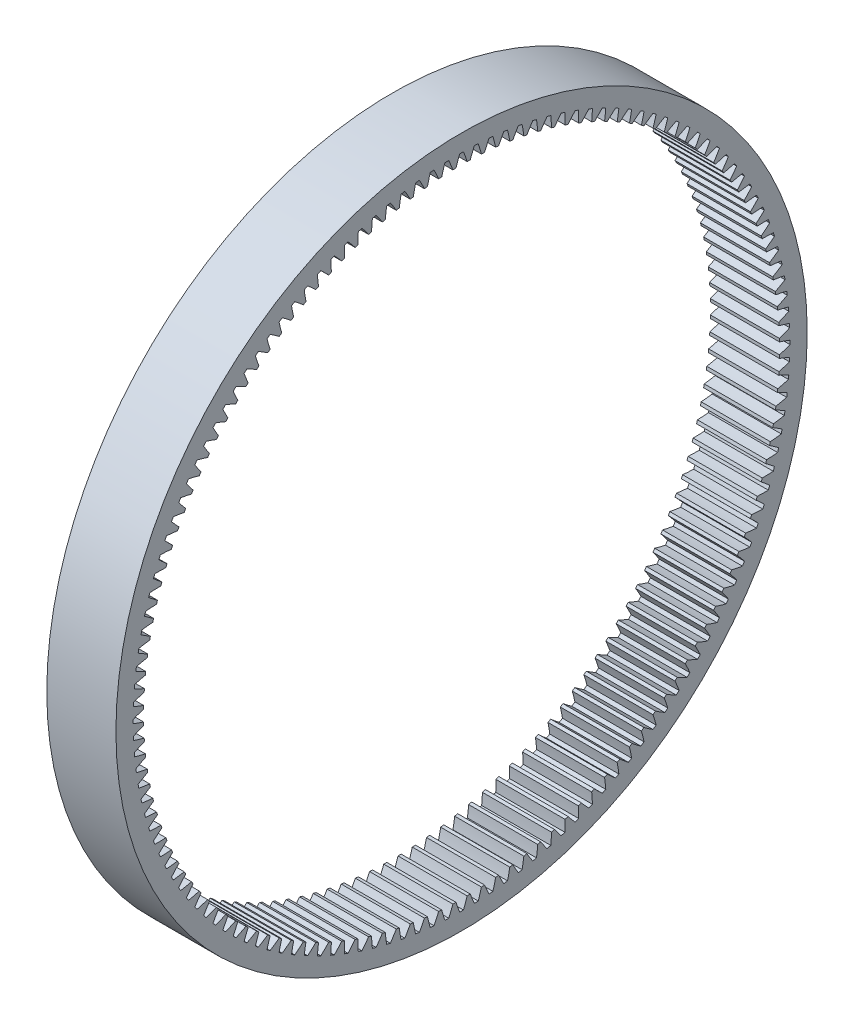
SolidWorks part; units mm, degrees
ref_plane "Plane1" through (0, 0, 0) normal (0, 0, 1) x (1, 0, 0)
ref_plane "Plane2" through (0, 0, 0) normal (0, 1, 0) x (1, 0, 0)
ref_plane "Plane3" through (0, 0, 0) normal (1, 0, 0) x (0, 0, -1)
other "Configuration Table"
sketch "HoldingSke" plane through (0, 0, 0) normal (0, 1, 0) x (1, 0, 0)
  line L0 (0, 0) -> (-0.9576, -0.8035)
  line L1 (-15, 0) -> (100, 0) construction
  line L2 (0, 0) -> (-2.1039, 2.3779)
  line L3 (0, 0) -> (-11.863, 4.5341)
  line L4 (0, 0) -> (-6.6156, 5.5511)
  line L5 (0, 0) -> (-23.7986, -8.8762)
  line L6 (0, 0) -> (-10.5278, -7.1032)
  line L7 (-2.1039, 2.3779) -> (3.3635, 27.1825)
  line L8 (-76.2, 3.1779) -> (-54.61, 3.1779)
  line L9 (-71.009, 38.7566) -> (-53.1078, 45.2721)
  line L10 (-76.2, 71.12) -> (104.1128, 71.12)
  line L11 (0, 0) -> (-12, 0)
  line L12 (-76.2, 101.6) -> (-76.17, 101.6)
  line L13 (24.9733, 27.94) -> (52.9518, 28.4284)
  line L14 (24.9733, 27.94) -> (24.9743, 27.94)
  line L15 (24.9733, 27.94) -> (100.4006, 29.5858)
  circle A0 centre (0, 0) radius 60
  circle A1 centre (0, 0) radius 12.7
  circle A2 centre (0, 0) radius 12.7
  dimension "Num_teeth" = 140
  dimension "Pitch_radius" = 180.3128
  dimension "Width" = 12
  dimension "Diameter" = 120
sketch "BasProSke" plane through (0, 0, 0) normal (0, 1, 0) x (1, 0, 0)
  line L0 (-10, 0) -> (60, 0) construction
  line L1 (0, 55.2) -> (0, 60)
  line L2 (0, 55.2) -> (12, 55.2)
  line L3 (12, 55.2) -> (12, 60)
  line L4 (12, 60) -> (0, 60)
  dimension "Thickness" = 12
  dimension "Diameter" = 120
revolve "Base-Revolve" add sketch "BasProSke" angle 360 about L0
sketch "TooCutSke" plane through (0, 0, 0) normal (1, 0, 0) x (0, 0, -1)
  line L3 (0.7033, 55.9956) -> (0.7033, 53.6633) construction
  line L4 (0, 0) -> (0, 59.563) construction
  line L5 (0, 0) -> (-1.5331, 68.3103) construction
  line L6 (-25.7418, 46.7947) -> (36.7706, 48.1977) construction
  circle A0 centre (0, 0) radius 56 construction
  circle A1 centre (0, 0) radius 57.001 construction
  circle A2 centre (0, 0) radius 47.3605 construction
  circle A3 centre (0, 0) radius 55.1746 construction
  arc A4 (0.9775, 55.1659) -> (0.3322, 57) centre (-25.7418, 46.7947) ccw
  arc A5 (0.9775, 55.1659) -> (-0.9775, 55.1659) centre (0, 0) ccw
  arc A6 (0.3322, 57) -> (-0.3322, 57) centre (0, 0) ccw
  arc A7 (-0.3322, 57) -> (-0.9775, 55.1659) centre (25.7418, 46.7947) ccw
extrude "ToothCut" cut sketch "TooCutSke" along normal through all
fillet "Breaks" [suppressed] radius 0.08
fillet "RootFillets" [suppressed] radius 0.201
pattern_circular "TeethCuts" count 140 every 2.571 about axis through (-10, 0, 0) along (1, 0, 0) of "RootFillets", "Breaks", "ToothCut"
equation "' \"Module@HoldingSke\" = 6.35"
equation "' \"Num_teeth@HoldingSke\" = 24"
equation "' \"Ap@HoldingSke\" =  14.5"
equation "' \"Ap@HoldingSke\" = 14.5"
equation "' \"Width@HoldingSke\" = 12"
equation "' \"Diameter@HoldingSke\" = 8 * 25.4"
equation "' \"Show_teeth@HoldingSke\" = 100"
equation "' \"Backlash@HoldingSke\" = 0.009 * 25.4"
equation "' \"Addendum_fac@HoldingSke\" = 1.0"
equation "' \"Dedendum_fac@HoldingSke\" = 1.25"
equation "' \"Dedendum_add@HoldingSke\" = 0.00005 * 25.4"
equation "' \"Clearance_fac@HoldingSke\" = 0.25"
equation "\"Pitch@HoldingSke\" = 1 / \"Module@HoldingSke\" "
equation "\"Overcut_dia@TooCutSke\" = (\"Num_teeth@HoldingSke\" - 2 * \"Addendum_fac@HoldingSke\") / \"Pitch@HoldingSke\" - 0.002 * 25.4"
equation "\"Pitch_dia@TooCutSke\" = \"Num_teeth@HoldingSke\" / \"Pitch@HoldingSke\""
equation "\"Base_dia@TooCutSke\" = \"Num_teeth@HoldingSke\" / \"Pitch@HoldingSke\" * cos((\"Ap@HoldingSke\"  * 3.14159265 / 180)) * 0.90"
equation "\"Root_dia@TooCutSke\" = \"Num_teeth@HoldingSke\"  / \"Pitch@HoldingSke\" + 2 *  \"Dedendum_fac@HoldingSke\"/ \"Pitch@HoldingSke\" + \"Dedendum_add@HoldingSke\" * 2"
equation "\"Half_ang@TooCutSke\" = 180 / \"Num_teeth@HoldingSke\""
equation "\"Half_CT@TooCutSke\" = \"Num_teeth@HoldingSke\" / \"Pitch@HoldingSke\" * sin((3.14159265 / 2 / \"Num_teeth@HoldingSke\")) / 2 + 10 * \"Backlash@HoldingSke\" / 4"
equation "\"Flank_rad@TooCutSke\" = \"Num_teeth@HoldingSke\" / \"Pitch@HoldingSke\" / 4"
equation "\"Radius@RootFillets\"= \"Clearance_fac@HoldingSke\" / \"Pitch@HoldingSke\" + \"Dedendum_add@HoldingSke\""
equation "\"Break_rad@Breaks\" = 0.02 / \"Pitch@HoldingSke\" * 5"
equation "\"Num_teeth@TeethCuts\" = int( \"Show_teeth@HoldingSke\" ) + 1"
equation "\"Num_teeth@TeethCuts\" = ((sgn( \"Num_teeth@TeethCuts\" - \"Num_teeth@HoldingSke\" )-1)*( \"Num_teeth@TeethCuts\" - \"Num_teeth@HoldingSke\" ))/-2+ \"Num_teeth@HoldingSke\""
equation "\"Num_teeth@TeethCuts\" = ((sgn( \"Num_teeth@TeethCuts\" - 2.0)+1)*( \"Num_teeth@TeethCuts\" - 2.0))/2 +2.0"
equation "\"Angle@TeethCuts\" = 360.0 / \"Num_teeth@HoldingSke\""
equation "\"Diameter@BasProSke\" = \"Num_teeth@HoldingSke\"  / \"Pitch@HoldingSke\" + 2 *  \"Dedendum_fac@HoldingSke\"/ \"Pitch@HoldingSke\" + \"Dedendum_add@HoldingSke\" * 2 + 0.002 * 25.4"
equation "\"Diameter@BasProSke\" = ((sgn( \"Diameter@BasProSke\"  - \"Diameter@HoldingSke\" )+1)*( \"Diameter@BasProSke\"  - \"Diameter@HoldingSke\" ))/2 + \"Diameter@HoldingSke\""
equation "\"Inside_diameter@BasProSke\" =  (\"Num_teeth@HoldingSke\" - 2 * \"Addendum_fac@HoldingSke\") / \"Pitch@HoldingSke\" "
equation "\"Thickness@BasProSke\"  = \"Width@HoldingSke\""
